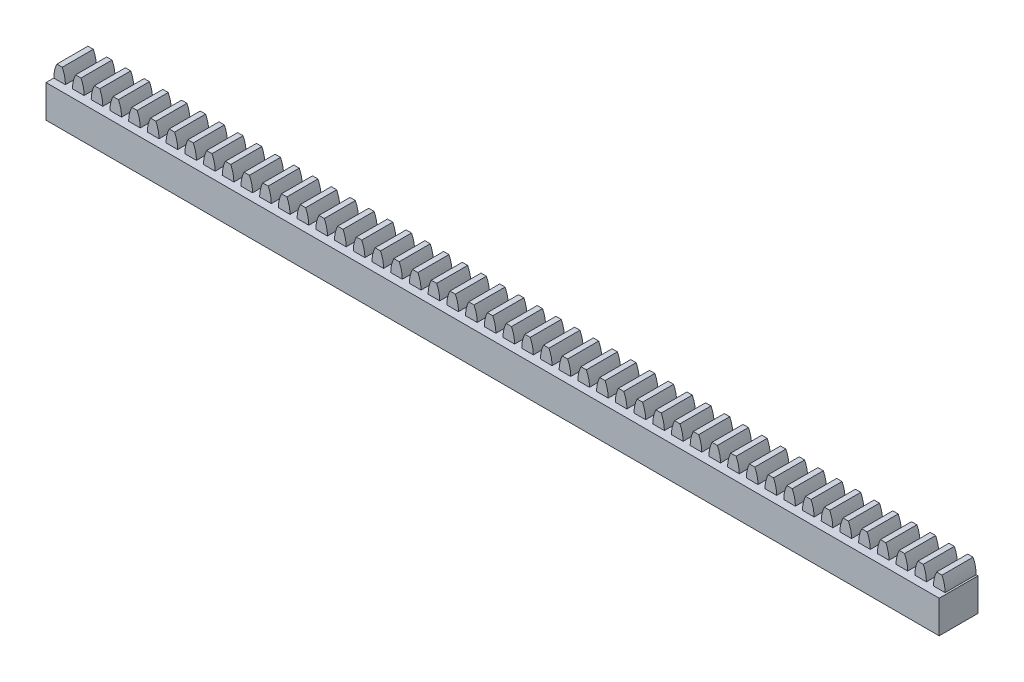
SolidWorks part; units mm, degrees
material "ABS"
ref_plane "Plano frontal" through (0, 0, 0) normal (0, 0, 1) x (1, 0, 0)
ref_plane "Plano superior" through (0, 0, 0) normal (0, 1, 0) x (1, 0, 0)
ref_plane "Plano direito" through (0, 0, 0) normal (1, 0, 0) x (0, 0, -1)
sketch "Esboço1" plane through (0, 0, 0) normal (0, 0, 1) x (1, 0, 0)
  line L0 (-1.7112, 4.5297) -> (-1.0175, 4.5297)
  line L1 (0.6988, 4.5297) -> (1.3925, 4.5297)
  line L2 (0.2978, 2.7713) -> (2.7078, 2.7713)
  line L3 (-2.1122, 2.7713) -> (0.2978, 2.7713)
  line L4 (3.1088, 4.5297) -> (3.8025, 4.5297)
  line L5 (2.7078, 2.7713) -> (5.1178, 2.7713)
  line L6 (5.5188, 4.5297) -> (6.2125, 4.5297)
  line L7 (5.1178, 2.7713) -> (7.5278, 2.7713)
  line L8 (7.9288, 4.5297) -> (8.6225, 4.5297)
  line L9 (7.5278, 2.7713) -> (9.9378, 2.7713)
  line L10 (10.3388, 4.5297) -> (11.0325, 4.5297)
  line L11 (9.9378, 2.7713) -> (12.3478, 2.7713)
  line L12 (12.7488, 4.5297) -> (13.4425, 4.5297)
  line L13 (12.3478, 2.7713) -> (14.7578, 2.7713)
  line L14 (15.1588, 4.5297) -> (15.8525, 4.5297)
  line L15 (14.7578, 2.7713) -> (17.1678, 2.7713)
  line L16 (17.5688, 4.5297) -> (18.2625, 4.5297)
  line L17 (17.1678, 2.7713) -> (19.5778, 2.7713)
  line L18 (19.9788, 4.5297) -> (20.6725, 4.5297)
  line L19 (19.5778, 2.7713) -> (21.9878, 2.7713)
  line L20 (22.3888, 4.5297) -> (23.0825, 4.5297)
  line L21 (21.9878, 2.7713) -> (24.3978, 2.7713)
  line L22 (24.7988, 4.5297) -> (25.4925, 4.5297)
  line L23 (24.3978, 2.7713) -> (26.8078, 2.7713)
  line L24 (27.2088, 4.5297) -> (27.9025, 4.5297)
  line L25 (26.8078, 2.7713) -> (29.2178, 2.7713)
  line L26 (29.6188, 4.5297) -> (30.3125, 4.5297)
  line L27 (29.2178, 2.7713) -> (31.6278, 2.7713)
  line L28 (32.0288, 4.5297) -> (32.7225, 4.5297)
  line L29 (31.6278, 2.7713) -> (34.0378, 2.7713)
  line L30 (34.4388, 4.5297) -> (35.1325, 4.5297)
  line L31 (34.0378, 2.7713) -> (36.4478, 2.7713)
  line L32 (36.8488, 4.5297) -> (37.5425, 4.5297)
  line L33 (36.4478, 2.7713) -> (38.8578, 2.7713)
  line L34 (39.2588, 4.5297) -> (39.9525, 4.5297)
  line L35 (38.8578, 2.7713) -> (41.2678, 2.7713)
  line L36 (41.6688, 4.5297) -> (42.3625, 4.5297)
  line L37 (41.2678, 2.7713) -> (43.6778, 2.7713)
  line L38 (44.0788, 4.5297) -> (44.7725, 4.5297)
  line L39 (43.6778, 2.7713) -> (46.0878, 2.7713)
  line L40 (46.4888, 4.5297) -> (47.1825, 4.5297)
  line L41 (46.0878, 2.7713) -> (48.4978, 2.7713)
  line L42 (77.4178, 2.7713) -> (77.4178, -1.4287)
  line L43 (48.8988, 4.5297) -> (49.5925, 4.5297)
  line L44 (48.4978, 2.7713) -> (50.9078, 2.7713)
  line L45 (51.3088, 4.5297) -> (52.0025, 4.5297)
  line L46 (50.9078, 2.7713) -> (53.3178, 2.7713)
  line L47 (53.7188, 4.5297) -> (54.4125, 4.5297)
  line L48 (53.3178, 2.7713) -> (55.7278, 2.7713)
  line L49 (56.1288, 4.5297) -> (56.8225, 4.5297)
  line L50 (55.7278, 2.7713) -> (58.1378, 2.7713)
  line L51 (58.5388, 4.5297) -> (59.2325, 4.5297)
  line L52 (58.1378, 2.7713) -> (60.5478, 2.7713)
  line L53 (60.9488, 4.5297) -> (61.6425, 4.5297)
  line L54 (60.5478, 2.7713) -> (62.9578, 2.7713)
  line L55 (63.3588, 4.5297) -> (64.0525, 4.5297)
  line L56 (62.9578, 2.7713) -> (65.3678, 2.7713)
  line L57 (65.7688, 4.5297) -> (66.4625, 4.5297)
  line L58 (65.3678, 2.7713) -> (67.7778, 2.7713)
  line L59 (68.1788, 4.5297) -> (68.8725, 4.5297)
  line L60 (67.7778, 2.7713) -> (70.1878, 2.7713)
  line L61 (70.5888, 4.5297) -> (71.2825, 4.5297)
  line L62 (70.1878, 2.7713) -> (72.5978, 2.7713)
  line L63 (72.9988, 4.5297) -> (73.6925, 4.5297)
  line L64 (72.5978, 2.7713) -> (75.0078, 2.7713)
  line L65 (75.4088, 4.5297) -> (76.1025, 4.5297)
  line L66 (75.0078, 2.7713) -> (77.4178, 2.7713)
  line L67 (77.4178, -1.4287) -> (47.8878, -1.4287)
  line L68 (77.4178, -1.4287) -> (112.8878, -1.4287)
  line L69 (112.8878, -1.4287) -> (77.4178, -1.4287)
  line L70 (77.8188, 4.5297) -> (78.5125, 4.5297)
  line L71 (77.4178, 2.7713) -> (79.8278, 2.7713)
  line L72 (80.2288, 4.5297) -> (80.9225, 4.5297)
  line L73 (79.8278, 2.7713) -> (82.2378, 2.7713)
  line L74 (82.6388, 4.5297) -> (83.3325, 4.5297)
  line L75 (82.2378, 2.7713) -> (84.6478, 2.7713)
  line L76 (85.0488, 4.5297) -> (85.7425, 4.5297)
  line L77 (84.6478, 2.7713) -> (87.0578, 2.7713)
  line L78 (87.4588, 4.5297) -> (88.1525, 4.5297)
  line L79 (87.0578, 2.7713) -> (89.4678, 2.7713)
  line L80 (89.8688, 4.5297) -> (90.5625, 4.5297)
  line L81 (89.4678, 2.7713) -> (91.8778, 2.7713)
  line L82 (92.2788, 4.5297) -> (92.9725, 4.5297)
  line L83 (91.8778, 2.7713) -> (94.2878, 2.7713)
  line L84 (94.6888, 4.5297) -> (95.3825, 4.5297)
  line L85 (94.2878, 2.7713) -> (96.6978, 2.7713)
  line L86 (97.0988, 4.5297) -> (97.7925, 4.5297)
  line L87 (96.6978, 2.7713) -> (99.1078, 2.7713)
  line L88 (99.5088, 4.5297) -> (100.2025, 4.5297)
  line L89 (99.1078, 2.7713) -> (101.5178, 2.7713)
  line L90 (101.9188, 4.5297) -> (102.6125, 4.5297)
  line L91 (101.5178, 2.7713) -> (103.9278, 2.7713)
  line L92 (104.3288, 4.5297) -> (105.0225, 4.5297)
  line L93 (103.9278, 2.7713) -> (106.3378, 2.7713)
  line L94 (106.7388, 4.5297) -> (107.4325, 4.5297)
  line L95 (106.3378, 2.7713) -> (108.7478, 2.7713)
  line L96 (109.1488, 4.5297) -> (109.8425, 4.5297)
  line L97 (108.7478, 2.7713) -> (111.1578, 2.7713)
  line L98 (111.5588, 4.5297) -> (112.2525, 4.5297)
  line L99 (111.1578, 2.7713) -> (112.8878, 2.7713)
  line L100 (112.8878, -1.4287) -> (112.8878, 2.7713)
  line L124 (-2.1122, 2.7713) -> (-2.1122, -1.4287)
  line L127 (-2.1122, -1.4287) -> (47.8878, -1.4287)
  line L128 (46.4888, 4.5297) -> (47.1825, 4.5297) [skipped]
  line L129 (46.0878, 2.7713) -> (47.5834, 2.7713) [skipped]
  line L130 (77.4178, 2.7713) -> (79.8278, 2.7713) [skipped]
  line L131 (77.8188, 4.5297) -> (78.5125, 4.5297) [skipped]
  arc A0 (-1.7112, 4.5297) -> (-2.1122, 2.7713) centre (1.944, 2.7713) ccw
  arc A1 (-1.0175, 4.5297) -> (-0.6166, 2.7713) centre (-4.6728, 2.7713) cw
  arc A2 (0.6988, 4.5297) -> (0.2978, 2.7713) centre (4.354, 2.7713) ccw
  arc A3 (1.3925, 4.5297) -> (1.7934, 2.7713) centre (-2.2628, 2.7713) cw
  arc A4 (3.1088, 4.5297) -> (2.7078, 2.7713) centre (6.764, 2.7713) ccw
  arc A5 (3.8025, 4.5297) -> (4.2034, 2.7713) centre (0.1472, 2.7713) cw
  arc A6 (5.5188, 4.5297) -> (5.1178, 2.7713) centre (9.174, 2.7713) ccw
  arc A7 (6.2125, 4.5297) -> (6.6134, 2.7713) centre (2.5572, 2.7713) cw
  arc A8 (7.9288, 4.5297) -> (7.5278, 2.7713) centre (11.584, 2.7713) ccw
  arc A9 (8.6225, 4.5297) -> (9.0234, 2.7713) centre (4.9672, 2.7713) cw
  arc A10 (10.3388, 4.5297) -> (9.9378, 2.7713) centre (13.994, 2.7713) ccw
  arc A11 (11.0325, 4.5297) -> (11.4334, 2.7713) centre (7.3772, 2.7713) cw
  arc A12 (12.7488, 4.5297) -> (12.3478, 2.7713) centre (16.404, 2.7713) ccw
  arc A13 (13.4425, 4.5297) -> (13.8434, 2.7713) centre (9.7872, 2.7713) cw
  arc A14 (15.1588, 4.5297) -> (14.7578, 2.7713) centre (18.814, 2.7713) ccw
  arc A15 (15.8525, 4.5297) -> (16.2534, 2.7713) centre (12.1972, 2.7713) cw
  arc A16 (17.5688, 4.5297) -> (17.1678, 2.7713) centre (21.224, 2.7713) ccw
  arc A17 (18.2625, 4.5297) -> (18.6634, 2.7713) centre (14.6072, 2.7713) cw
  arc A18 (19.9788, 4.5297) -> (19.5778, 2.7713) centre (23.634, 2.7713) ccw
  arc A19 (20.6725, 4.5297) -> (21.0734, 2.7713) centre (17.0172, 2.7713) cw
  arc A20 (22.3888, 4.5297) -> (21.9878, 2.7713) centre (26.044, 2.7713) ccw
  arc A21 (23.0825, 4.5297) -> (23.4834, 2.7713) centre (19.4272, 2.7713) cw
  arc A22 (24.7988, 4.5297) -> (24.3978, 2.7713) centre (28.454, 2.7713) ccw
  arc A23 (25.4925, 4.5297) -> (25.8934, 2.7713) centre (21.8372, 2.7713) cw
  arc A24 (27.2088, 4.5297) -> (26.8078, 2.7713) centre (30.864, 2.7713) ccw
  arc A25 (27.9025, 4.5297) -> (28.3034, 2.7713) centre (24.2472, 2.7713) cw
  arc A26 (29.6188, 4.5297) -> (29.2178, 2.7713) centre (33.274, 2.7713) ccw
  arc A27 (30.3125, 4.5297) -> (30.7134, 2.7713) centre (26.6572, 2.7713) cw
  arc A28 (32.0288, 4.5297) -> (31.6278, 2.7713) centre (35.684, 2.7713) ccw
  arc A29 (32.7225, 4.5297) -> (33.1234, 2.7713) centre (29.0672, 2.7713) cw
  arc A30 (34.4388, 4.5297) -> (34.0378, 2.7713) centre (38.094, 2.7713) ccw
  arc A31 (35.1325, 4.5297) -> (35.5334, 2.7713) centre (31.4772, 2.7713) cw
  arc A32 (36.8488, 4.5297) -> (36.4478, 2.7713) centre (40.504, 2.7713) ccw
  arc A33 (37.5425, 4.5297) -> (37.9434, 2.7713) centre (33.8872, 2.7713) cw
  arc A34 (39.2588, 4.5297) -> (38.8578, 2.7713) centre (42.914, 2.7713) ccw
  arc A35 (39.9525, 4.5297) -> (40.3534, 2.7713) centre (36.2972, 2.7713) cw
  arc A36 (41.6688, 4.5297) -> (41.2678, 2.7713) centre (45.324, 2.7713) ccw
  arc A37 (42.3625, 4.5297) -> (42.7634, 2.7713) centre (38.7072, 2.7713) cw
  arc A38 (44.0788, 4.5297) -> (43.6778, 2.7713) centre (47.734, 2.7713) ccw
  arc A39 (44.7725, 4.5297) -> (45.1734, 2.7713) centre (41.1172, 2.7713) cw
  arc A40 (46.4888, 4.5297) -> (46.0878, 2.7713) centre (50.144, 2.7713) ccw
  arc A41 (47.1825, 4.5297) -> (47.5834, 2.7713) centre (43.5272, 2.7713) cw
  arc A42 (47.1825, 4.5297) -> (47.5834, 2.7713) centre (43.5272, 2.7713) cw [skipped]
  arc A43 (46.4888, 4.5297) -> (46.0878, 2.7713) centre (50.144, 2.7713) ccw [skipped]
  arc A44 (48.8988, 4.5297) -> (48.4978, 2.7713) centre (52.554, 2.7713) ccw
  arc A45 (49.5925, 4.5297) -> (49.9934, 2.7713) centre (45.9372, 2.7713) cw
  arc A46 (51.3088, 4.5297) -> (50.9078, 2.7713) centre (54.964, 2.7713) ccw
  arc A47 (52.0025, 4.5297) -> (52.4034, 2.7713) centre (48.3472, 2.7713) cw
  arc A48 (53.7188, 4.5297) -> (53.3178, 2.7713) centre (57.374, 2.7713) ccw
  arc A49 (54.4125, 4.5297) -> (54.8134, 2.7713) centre (50.7572, 2.7713) cw
  arc A50 (56.1288, 4.5297) -> (55.7278, 2.7713) centre (59.784, 2.7713) ccw
  arc A51 (56.8225, 4.5297) -> (57.2234, 2.7713) centre (53.1672, 2.7713) cw
  arc A52 (58.5388, 4.5297) -> (58.1378, 2.7713) centre (62.194, 2.7713) ccw
  arc A53 (59.2325, 4.5297) -> (59.6334, 2.7713) centre (55.5772, 2.7713) cw
  arc A54 (60.9488, 4.5297) -> (60.5478, 2.7713) centre (64.604, 2.7713) ccw
  arc A55 (61.6425, 4.5297) -> (62.0434, 2.7713) centre (57.9872, 2.7713) cw
  arc A56 (63.3588, 4.5297) -> (62.9578, 2.7713) centre (67.014, 2.7713) ccw
  arc A57 (64.0525, 4.5297) -> (64.4534, 2.7713) centre (60.3972, 2.7713) cw
  arc A58 (65.7688, 4.5297) -> (65.3678, 2.7713) centre (69.424, 2.7713) ccw
  arc A59 (66.4625, 4.5297) -> (66.8634, 2.7713) centre (62.8072, 2.7713) cw
  arc A60 (68.1788, 4.5297) -> (67.7778, 2.7713) centre (71.834, 2.7713) ccw
  arc A61 (68.8725, 4.5297) -> (69.2734, 2.7713) centre (65.2172, 2.7713) cw
  arc A62 (70.5888, 4.5297) -> (70.1878, 2.7713) centre (74.244, 2.7713) ccw
  arc A63 (71.2825, 4.5297) -> (71.6834, 2.7713) centre (67.6272, 2.7713) cw
  arc A64 (72.9988, 4.5297) -> (72.5978, 2.7713) centre (76.654, 2.7713) ccw
  arc A65 (73.6925, 4.5297) -> (74.0934, 2.7713) centre (70.0372, 2.7713) cw
  arc A66 (75.4088, 4.5297) -> (75.0078, 2.7713) centre (79.064, 2.7713) ccw
  arc A67 (76.1025, 4.5297) -> (76.5034, 2.7713) centre (72.4472, 2.7713) cw
  arc A68 (77.8188, 4.5297) -> (77.4178, 2.7713) centre (81.474, 2.7713) ccw
  arc A69 (78.5125, 4.5297) -> (78.9134, 2.7713) centre (74.8572, 2.7713) cw
  arc A70 (78.5125, 4.5297) -> (78.9134, 2.7713) centre (74.8572, 2.7713) cw [skipped]
  arc A71 (77.8188, 4.5297) -> (77.4178, 2.7713) centre (81.474, 2.7713) ccw [skipped]
  arc A72 (80.2288, 4.5297) -> (79.8278, 2.7713) centre (83.884, 2.7713) ccw
  arc A73 (80.9225, 4.5297) -> (81.3234, 2.7713) centre (77.2672, 2.7713) cw
  arc A74 (82.6388, 4.5297) -> (82.2378, 2.7713) centre (86.294, 2.7713) ccw
  arc A75 (83.3325, 4.5297) -> (83.7334, 2.7713) centre (79.6772, 2.7713) cw
  arc A76 (85.0488, 4.5297) -> (84.6478, 2.7713) centre (88.704, 2.7713) ccw
  arc A77 (85.7425, 4.5297) -> (86.1434, 2.7713) centre (82.0872, 2.7713) cw
  arc A78 (87.4588, 4.5297) -> (87.0578, 2.7713) centre (91.114, 2.7713) ccw
  arc A79 (88.1525, 4.5297) -> (88.5534, 2.7713) centre (84.4972, 2.7713) cw
  arc A80 (89.8688, 4.5297) -> (89.4678, 2.7713) centre (93.524, 2.7713) ccw
  arc A81 (90.5625, 4.5297) -> (90.9634, 2.7713) centre (86.9072, 2.7713) cw
  arc A82 (92.2788, 4.5297) -> (91.8778, 2.7713) centre (95.934, 2.7713) ccw
  arc A83 (92.9725, 4.5297) -> (93.3734, 2.7713) centre (89.3172, 2.7713) cw
  arc A84 (94.6888, 4.5297) -> (94.2878, 2.7713) centre (98.344, 2.7713) ccw
  arc A85 (95.3825, 4.5297) -> (95.7834, 2.7713) centre (91.7272, 2.7713) cw
  arc A86 (97.0988, 4.5297) -> (96.6978, 2.7713) centre (100.754, 2.7713) ccw
  arc A87 (97.7925, 4.5297) -> (98.1934, 2.7713) centre (94.1372, 2.7713) cw
  arc A88 (99.5088, 4.5297) -> (99.1078, 2.7713) centre (103.164, 2.7713) ccw
  arc A89 (100.2025, 4.5297) -> (100.6034, 2.7713) centre (96.5472, 2.7713) cw
  arc A90 (101.9188, 4.5297) -> (101.5178, 2.7713) centre (105.574, 2.7713) ccw
  arc A91 (102.6125, 4.5297) -> (103.0134, 2.7713) centre (98.9572, 2.7713) cw
  arc A92 (104.3288, 4.5297) -> (103.9278, 2.7713) centre (107.984, 2.7713) ccw
  arc A93 (105.0225, 4.5297) -> (105.4234, 2.7713) centre (101.3672, 2.7713) cw
  arc A94 (106.7388, 4.5297) -> (106.3378, 2.7713) centre (110.394, 2.7713) ccw
  arc A95 (107.4325, 4.5297) -> (107.8334, 2.7713) centre (103.7772, 2.7713) cw
  arc A96 (109.1488, 4.5297) -> (108.7478, 2.7713) centre (112.804, 2.7713) ccw
  arc A97 (109.8425, 4.5297) -> (110.2434, 2.7713) centre (106.1872, 2.7713) cw
  arc A98 (111.5588, 4.5297) -> (111.1578, 2.7713) centre (115.214, 2.7713) ccw
  arc A99 (112.2525, 4.5297) -> (112.6534, 2.7713) centre (108.5972, 2.7713) cw
  dimension "D8" = 16
  dimension "D1" = 0.9144
  dimension "D2" = 115
  dimension "D3" = 21
  dimension "D4" = 0.6937
  dimension "D5" = 1.4956
  dimension "D7" = 79.53
  dimension "D10" = 4.2
  dimension "D6" = 15
extrude "Ressalto-extrusão1" add sketch "Esboço1" along normal mid plane 4 contours A1 L0 A0 L3 | A3 L1 A2 L2 | A5 L4 A4 L5 | A7 L6 A6 L7 | A9 L8 A8 L9 | A11 L10 A10 L11 | A13 L12 A12 L13 | A15 L14 A14 L15 | A17 L16 A16 L17 | A19 L18 A18 L19 | A21 L20 A20 L21 | A23 L22 A22 L23 | A25 L24 A24 L25 | A27 L26 A26 L27 | A29 L28 A28 L29 | A31 L30 A30 L31 | A33 L32 A32 L33 | A35 L34 A34 L35 | A37 L36 A36 L37 | A39 L38 A38 L39 | L40 A40 | A45 L43 A44 L44 | A47 L45 A46 L46 | A49 L47 A48 L48 | A51 L49 A50 L50 | A53 L51 A52 L52 | A55 L53 A54 L54 | A57 L55 A56 L56 | A59 L57 A58 L58 | A61 L59 A60 L60 | A63 L61 A62 L62 | A65 L63 A64 L64 | A67 L65 A66 L66 | A69 L70 A68 L71 | A73 L72 A72 L73 | A75 L74 A74 L75 | A77 L76 A76 L77 | A79 L78 A78 L79 | A81 L80 A80 L81 | A83 L82 A82 L83 | A85 L84 A84 L85 | A87 L86 A86 L87 | A89 L88 A88 L89 | A91 L90 A90 L91 | A93 L92 A92 L93 | A95 L94 A94 L95 | A97 L96 A96 L97 | A99 L98 A98 L99 region at (-1.3644, 3.5563, 0) region at (1.0456, 3.5563, 0) region at (3.4556, 3.5563, 0) region at (78.1656, 3.5563, 0) region at (75.7556, 3.5563, 0) region at (5.8656, 3.5563, 0) region at (80.5756, 3.5563, 0) region at (111.9056, 3.5563, 0) region at (73.3456, 3.5563, 0) region at (8.2756, 3.5563, 0) region at (82.9856, 3.5563, 0) region at (109.4956, 3.5563, 0) region at (70.9356, 3.5563, 0) region at (10.6856, 3.5563, 0) region at (85.3956, 3.5563, 0) region at (107.0856, 3.5563, 0) region at (68.5256, 3.5563, 0) region at (13.0956, 3.5563, 0) region at (87.8056, 3.5563, 0) region at (104.6756, 3.5563, 0) region at (66.1156, 3.5563, 0) region at (15.5056, 3.5563, 0) region at (90.2156, 3.5563, 0) region at (102.2656, 3.5563, 0) region at (63.7056, 3.5563, 0) region at (17.9156, 3.5563, 0) region at (92.6256, 3.5563, 0) region at (99.8556, 3.5563, 0) region at (61.2956, 3.5563, 0) region at (20.3256, 3.5563, 0) region at (95.0356, 3.5563, 0) region at (97.4456, 3.5563, 0) region at (58.8856, 3.5563, 0) region at (22.7356, 3.5563, 0) region at (56.4756, 3.5563, 0) region at (25.1456, 3.5563, 0) region at (54.0656, 3.5563, 0) region at (27.5556, 3.5563, 0) region at (51.6556, 3.5563, 0) region at (29.9656, 3.5563, 0) region at (49.2456, 3.5563, 0) region at (32.3756, 3.5563, 0) region at (46.8356, 3.5563, 0) region at (34.7856, 3.5563, 0) region at (44.4256, 3.5563, 0) region at (37.1956, 3.5563, 0) region at (42.0156, 3.5563, 0) region at (39.6056, 3.5563, 0)
extrude "Ressalto-extrusão2" add sketch "Esboço1<7>" along normal blind 3 and the other way blind 2 contours L124 L127 L39 L37 L35 L33 L31 L29 L27 L25 L23 L21 L19 L17 L15 L13 L11 L9 L7 L5 L2 L3 | L68 L100 L99 L97 L95 L93 L91 L89 L87 L85 L83 L81 L79 L77 L75 L73 L71 L42 region at (37.6528, 0.6713, 0) region at (95.1528, 0.6713, 0)
sketch "Esboço1<7>" plane through (0, 0, 0) normal (0, 0, 1) x (1, 0, 0) same geometry as "Esboço1"
